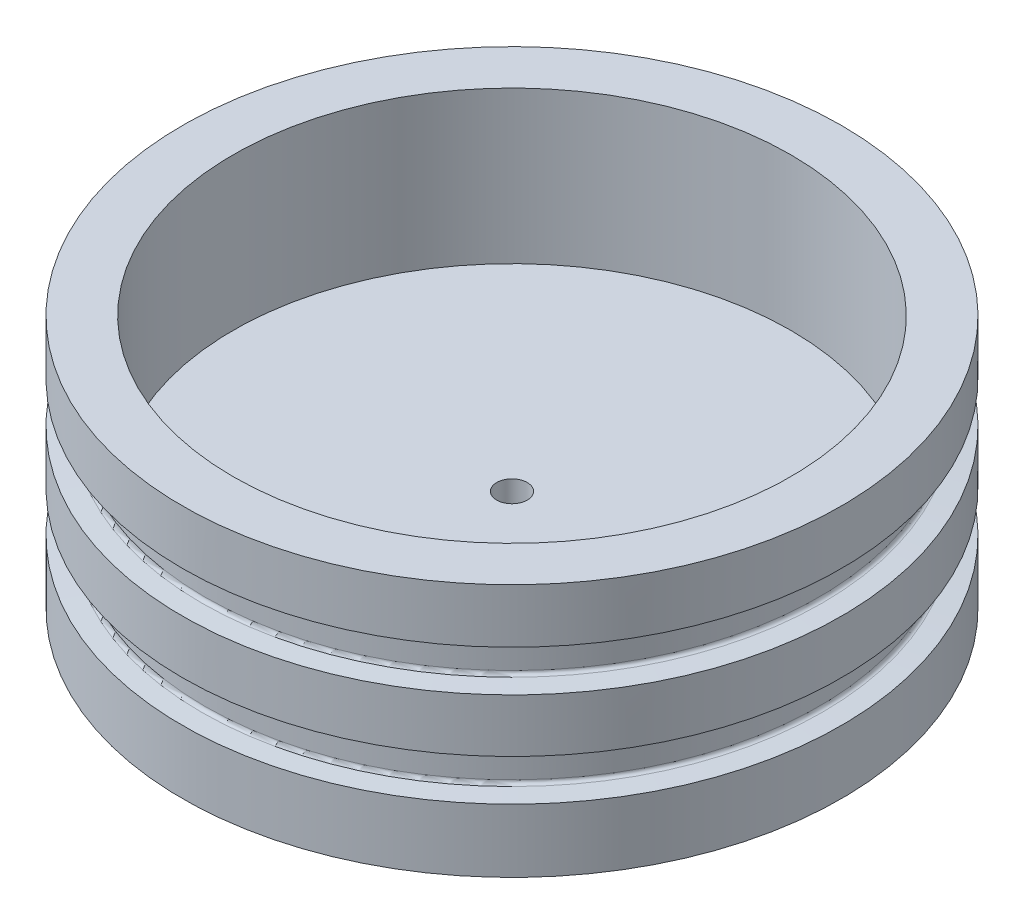
SolidWorks part; units mm, degrees
material "1060 Alloy"
ref_plane "Front Plane" through (0, 0, 0) normal (0, 0, 1) x (1, 0, 0)
ref_plane "Top Plane" through (0, 0, 0) normal (0, 1, 0) x (1, 0, 0)
ref_plane "Right Plane" through (0, 0, 0) normal (1, 0, 0) x (0, 0, -1)
sketch "Sketch1" plane through (0, 0, 0) normal (0, 0, 1) x (1, 0, 0)
  line L0 (0, 0) -> (0, 25.4) construction
  line L1 (-41.275, 13.97) -> (-41.275, 45.72)
  line L2 (-41.275, 13.97) -> (-5.1435, 13.97)
  line L3 (-1.9133, 0) -> (-1.9133, 26.67)
  line L4 (-1.9133, 26.67) -> (-34.925, 26.67)
  line L5 (-34.925, 26.67) -> (-34.925, 45.72)
  line L6 (-34.925, 45.72) -> (-41.275, 45.72)
  line L8 (-1.9133, 0) -> (-5.1435, 0)
  line L9 (-5.1435, 0) -> (-5.1435, 13.97)
  line L11 (55, 0) -> (-55, 0) construction
  dimension "D1" = 1.9133
  dimension "D2" = 34.925
  dimension "D3" = 31.75
  dimension "D4" = 6.35
  dimension "D5" = 12.7
  dimension "D6" = 13.97
  dimension "D7" = 5.1435
revolve "Revolve1" add sketch "Sketch1" angle 360 about L0
ref_plane "Plane1" through (0, 0, 0) normal (-1, 0, 0) x (0, 0, -1)
ref_plane "Plane2" through (0, 0, 0) normal (-1, 0, 0) x (0, 0, -1)
ref_plane "Plane3" through (0, 0, 0) normal (-1, 0, 0) x (0, 0, -1)
ref_plane "Plane4" through (0, 0, 0) normal (-1, 0, 0) x (0, 0, -1)
ref_plane "Plane5" through (0, 0, 0) normal (-1, 0, 0) x (0, 0, -1)
ref_plane "Plane6" through (0, 0, 0) normal (-1, 0, 0) x (0, 0, -1)
ref_plane "Plane7" through (0, 0, 0) normal (-1, 0, 0) x (0, 0, -1)
ref_plane "Plane8" through (0, 0, 0) normal (-1, 0, 0) x (0, 0, -1)
ref_plane "Plane9" through (0, 0, 0) normal (-1, 0, 0) x (0, 0, -1)
ref_plane "Plane10" through (0, 0, 0) normal (-1, 0, 0) x (0, 0, -1)
sketch "Sketch7" plane through (0, 0, 0) normal (-1, 0, 0) x (0, 0, -1)
  line L0 (38.8614, -33.9779) -> (41.3639, -33.759)
  line L1 (41.3639, -33.759) -> (41.3639, -38.9467)
  line L2 (41.3639, -38.9467) -> (38.8614, -38.7277)
  line L3 (38.4556, -38.2849) -> (38.4556, -34.4207)
  line L4 (0, 50) -> (0, -50) construction
  line L5 (-41.275, -45.72) -> (41.275, -45.72) construction
  arc A0 (38.8614, -38.7277) -> (38.4556, -38.2849) centre (38.9001, -38.2849) cw
  arc A1 (38.4556, -34.4207) -> (38.8614, -33.9779) centre (38.9001, -34.4207) cw
  dimension "D5" = 0.4445
  dimension "D6" = 0.4445
  dimension "D1" = 2.5121
  dimension "D2" = 3.8642
  dimension "D3" = 5.1877
  dimension "D4" = 2.5121
  dimension "D7" = 2.9083
  dimension "D8" = 6.7733
revolve "Groove for AS 568-234, O-Ring1" cut sketch "Sketch7"
pattern_linear "LPattern1" count 2 spacing 11.8533 along (0, -1, 0) of "Groove for AS 568-234, O-Ring1"
